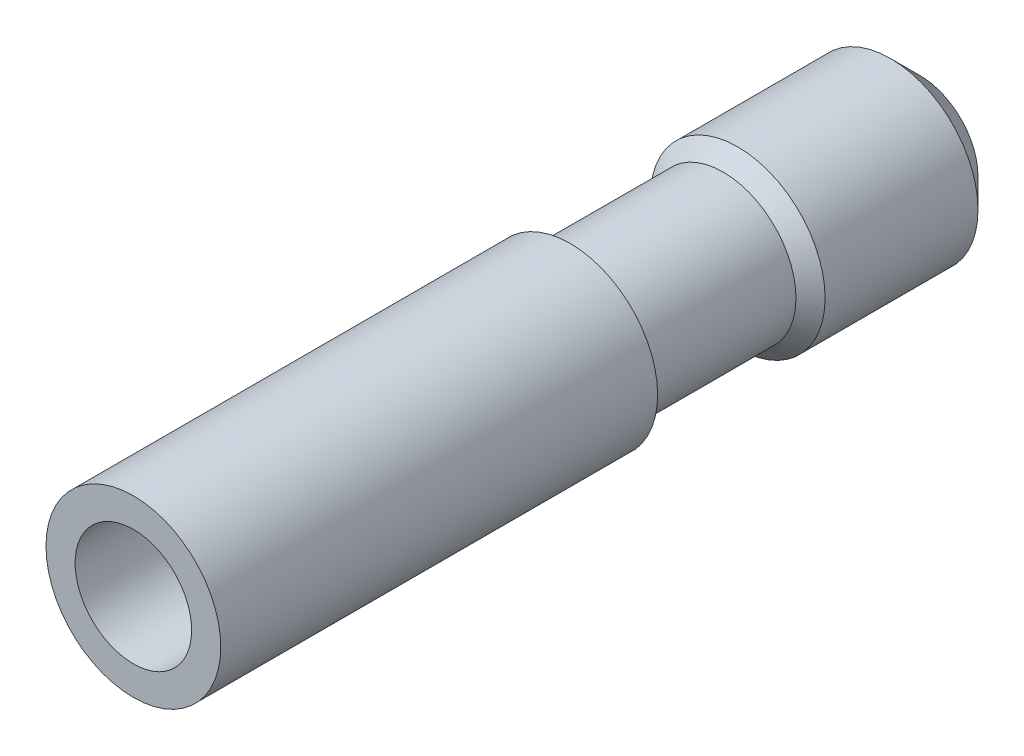
SolidWorks part; units mm, degrees
ref_plane "Plan de face" through (0, 0, 0) normal (0, 0, 1) x (1, 0, 0)
ref_plane "Plan de dessus" through (0, 0, 0) normal (0, 1, 0) x (1, 0, 0)
ref_plane "Plan de droite" through (0, 0, 0) normal (1, 0, 0) x (0, 0, -1)
sketch "Esquisse1" plane through (0, 0, 0) normal (0, 0, 1) x (1, 0, 0)
  circle A0 centre (0, 0) radius 3
  dimension "D1" = 6
extrude "Boss.-Extru.1" add sketch "Esquisse1" along normal blind 27 contours A0
cosmetic thread "Représentation de filetage1" parameters "D1"=5, "D2"=4.891
hole_wizard "Diamètre du perçage Ø4.0 (4)1" positions "Esquisse3" profile "Esquisse2" hole size "Ø4.0" standard "ISO"
sketch "Esquisse3" plane through (0, 0, 27) normal (0, 0, 1) x (1, 0, 0)
  point P0 (0, 0)
sketch "Esquisse2" plane through (0, 0, 27) normal (1, 0, 0) x (0, -1, 0)
  line L0 (0, 0) -> (0, 25.7017)
  line L1 (0, 25.7017) -> (2, 24.5)
  line L2 (2, 24.5) -> (2, 0)
  line L5 (2, 0) -> (0, 0)
  line L10 (0, 25.7017) -> (-2, 24.5) construction
  line L11 (0, -6.35) -> (0, 107.95) construction
  dimension "Diamètre du perçage" = 4
  dimension "Profondeur du perçage" = 24.5
  dimension "Angle de pointe" = 118
hole_wizard "Diamètre du perçage Ø2.5 (2.5)2" positions "Esquisse5" profile "Esquisse4" hole size "Ø2.5" standard "ISO"
sketch "Esquisse5" plane through (0, 0, 0) normal (0, 0, -1) x (-1, 0, 0)
  point P0 (0, 0)
sketch "Esquisse4" plane through (0, 0, 0) normal (1, 0, 0) x (0, 1, 0)
  line L0 (0, 0) -> (0, 3.7511)
  line L1 (0, 3.7511) -> (1.25, 3)
  line L2 (1.25, 3) -> (1.25, 0)
  line L5 (1.25, 0) -> (0, 0)
  line L10 (0, 3.7511) -> (-1.25, 3) construction
  line L11 (0, -6.35) -> (0, 107.95) construction
  dimension "Diamètre du perçage" = 2.5
  dimension "Profondeur du perçage" = 3
  dimension "Angle de pointe" = 118
sketch "Esquisse6" plane through (0, 0, 27) normal (0, 0, 1) x (1, 0, 0)
  line L1 (-6.0949, -5.2635) -> (5.6553, -5.2635)
  line L2 (-6.0949, -5.2635) -> (-6.0949, 6.1211)
  line L3 (-6.0949, 6.1211) -> (5.6553, 6.1211)
  line L4 (5.6553, -5.2635) -> (5.6553, 6.1211)
  circle A0 centre (0, 0) radius 2.5
  dimension "D1" = 5
extrude "Enlèv. mat.-Extru.1" cut sketch "Esquisse6" against normal blind 6 from offset 15 offset against normal yes
chamfer "Chanfrein1" distance 1 angle 45 1 edges at (3, 0, 0)
chamfer "Chanfrein2" distance 0.75 angle 45 1 edges at (2.5, 0, 6)
